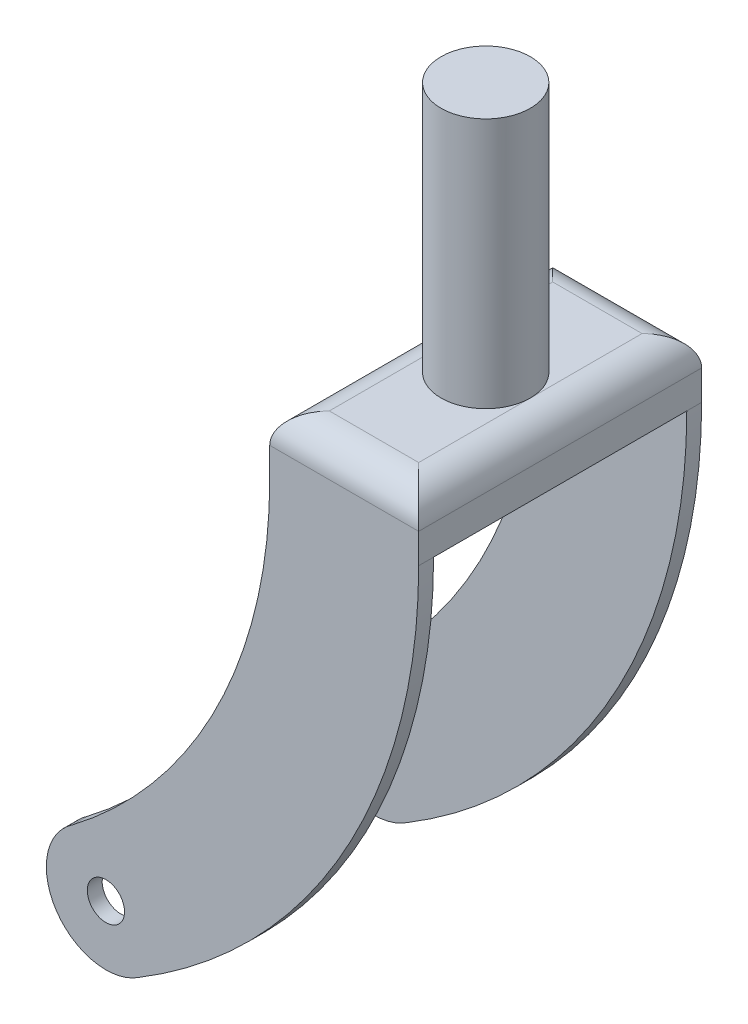
SolidWorks part; units mm, degrees
ref_plane "Alzado" through (0, 0, 0) normal (0, 0, 1) x (1, 0, 0)
ref_plane "Planta" through (0, 0, 0) normal (0, 1, 0) x (1, 0, 0)
ref_plane "Vista lateral" through (0, 0, 0) normal (1, 0, 0) x (0, 0, -1)
sketch "Croquis1" plane through (0, 0, 0) normal (0, 0, 1) x (1, 0, 0)
  line L0 (-7.0751, 10.5467) -> (7.0751, -10.5467) construction
  line L1 (-10.5467, -7.0751) -> (0, 0) construction
  line L2 (34.925, 95.25) -> (34.925, 107.95)
  line L3 (34.925, 107.95) -> (66.675, 107.95)
  line L4 (66.675, 107.95) -> (66.675, 95.25)
  line L5 (50.8, 107.95) -> (50.8, 95.25) construction
  circle A0 centre (0, 0) radius 3.969
  arc A1 (-7.0751, 10.5467) -> (7.0751, -10.5467) centre (0, 0) ccw
  arc A2 (-7.0751, 10.5467) -> (34.925, 95.25) centre (-71.4873, 95.25) ccw
  arc A3 (0, 0) -> (50.8, 95.25) centre (-63.8969, 95.25) ccw construction
  arc A4 (7.0751, -10.5467) -> (66.675, 95.25) centre (-57.0256, 95.25) ccw
  point P52 (50.8, 101.6)
  dimension "D1" = 7.938
  dimension "D2" = 25.4
  dimension "D3" = 31.75
  dimension "D4" = 50.8
  dimension "D5" = 95.25
  dimension "D6" = 12.7
extrude "Saliente-Extruir1" add sketch "Croquis1" along normal blind 30.1625 and the other way blind 30.1625
sketch "Croquis2" plane through (66.675, 0, 0) normal (1, 0, 0) x (0, 0, -1)
  line L0 (30.1625, 95.25) -> (-30.1625, 95.25) construction
  line L1 (-26.9875, 95.25) -> (26.9875, 95.25)
  line L2 (-26.9875, 95.25) -> (-26.9875, -31.75)
  line L3 (-26.9875, -31.75) -> (26.9875, -31.75)
  line L4 (26.9875, 95.25) -> (26.9875, -31.75)
  line L5 (0, 95.25) -> (0, 0) construction
  dimension "D1" = 53.975
  dimension "D2" = 127
extrude "Cortar-Extruir1" cut sketch "Croquis2" against normal through all
sketch "Croquis3" plane through (0, 107.95, 0) normal (0, 1, 0) x (1, 0, 0)
  line L0 (34.925, 0) -> (66.675, 0) construction
  line L1 (34.925, 30.1625) -> (34.925, -30.1625) construction
  line L2 (66.675, 30.1625) -> (66.675, -30.1625) construction
  circle A0 centre (50.8, 0) radius 9.525
  dimension "D1" = 19.05
extrude "Saliente-Extruir2" add sketch "Croquis3" along normal blind 53.5
fillet "Redondeo1" radius 6.35 4 edges at (50.8, 107.95, -30.1625) (66.675, 107.95, 0) (50.8, 107.95, 30.1625) (34.925, 107.95, 0)
